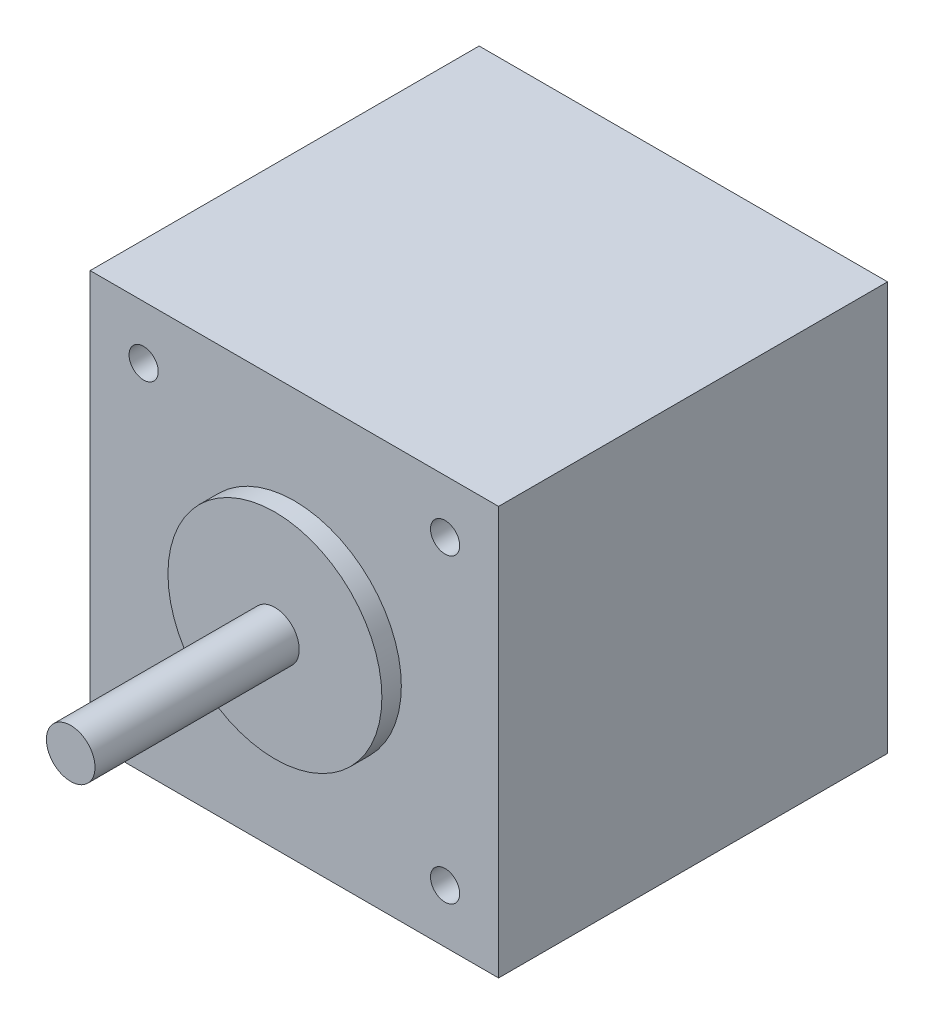
SolidWorks part; units mm, degrees
ref_plane "Спереди" through (0, 0, 0) normal (0, 0, 1) x (1, 0, 0)
ref_plane "Сверху" through (0, 0, 0) normal (0, 1, 0) x (1, 0, 0)
ref_plane "Справа" through (0, 0, 0) normal (1, 0, 0) x (0, 0, -1)
other "Configuration Table"
sketch "Эскиз1" plane through (0, 0, 0) normal (0, 0, 1) x (1, 0, 0)
  line L1 (-21, -21) -> (21, -21)
  line L2 (-21, -21) -> (-21, 21)
  line L3 (-21, 21) -> (21, 21)
  line L4 (21, -21) -> (21, 21)
  line L5 (-21, -21) -> (21, 21) construction
  line L6 (-21, 21) -> (21, -21) construction
  point P0 (0, 0)
  dimension "D1" = 42
  dimension "D2" = 42
extrude "Корпус" add sketch "Эскиз1" along normal blind 40
sketch "Эскиз2" plane through (0, 0, 0) normal (0, 0, 1) x (1, 0, 0)
  circle A0 centre (0, 0) radius 2.5
extrude "Вал_ПРЕДВ" add sketch "Эскиз2" along normal blind 63
sketch "Эскиз3" plane through (0, 0, 0) normal (0, 0, 1) x (1, 0, 0)
  circle A0 centre (0, 0) radius 11
  dimension "D1" = 22
extrude "Буртик_ПРЕДВ" add sketch "Эскиз3" along normal blind 42
sketch "Эскиз4" plane through (0, 0, 0) normal (0, 0, 1) x (1, 0, 0)
  circle A0 centre (-15.5, -15.5) radius 1.5
  circle A1 centre (-15.5, 15.5) radius 1.5
  circle A2 centre (15.5, -15.5) radius 1.5
  circle A3 centre (15.5, 15.5) radius 1.5
  dimension "D1" = 3
  dimension "D2" = 3
  dimension "D3" = 3
  dimension "D4" = 3
extrude "Крепеж_М3_ПРЕДВ" cut sketch "Эскиз4" against normal blind 4.5 from offset 40
equation "\"Мотор X ширина корпуса\"= 42.3"
equation "\"Мотор X высота корпуса\"= 42.3"
equation "\"Мотор X длина корпуса\"= 40"
equation "\"Мотор X вылет вала\"= 19.8"
equation "\"Мотор Y ширина корпуса\"= 42.3"
equation "\"Мотор Y высота корпуса\"= 42.3"
equation "\"Мотор Y длина корпуса\"= 48"
equation "\"Мотор Y вылет вала\"= 30"
equation "\"Мотор Z ширина корпуса\"= 42"
equation "\"Мотор Z высота корпуса\"= 42"
equation "\"Мотор Z длина корпуса\"= 40"
equation "\"Мотор Z вылет вала\"= 23"
equation "\"Мотор диаметр вала ПРЕДВ\"= 5"
equation "\"Мотор шаг крепления ПРЕДВ\"= 31"
equation "\"Мотор диаметр отверстий ПРЕДВ\"= 3"
equation "\"Мотор глубина отверстий ПРЕДВ\"= 4.5"
equation "\"Мотор диаметр буртика ПРЕДВ\"= 22"
equation "\"Мотор высота буртика ПРЕДВ\"= 2"
equation "\"Мотор диаметр шкива ПРЕДВ\"= 16"
equation "\"Мотор длина шкива ПРЕДВ\"= 12"
equation "\"Мотор отступ шкива ПРЕДВ\"= 5"
equation "\"Мотор X шаг градусов\"= 1.8"
equation "\"Мотор X ток А\"= 1.5"
equation "\"Мотор X сопротивление Ом\"= 1.3"
equation "\"Мотор X индуктивность мГн\"= 2"
equation "\"Мотор Y шаг градусов\"= 1.8"
equation "\"Мотор Y ток А\"= 2.2"
equation "\"Мотор Y сопротивление Ом\"= 0.9"
equation "\"Мотор Y индуктивность мГн\"= 2"
equation "\"Мотор Z шаг градусов\"= 1.8"
equation "\"Мотор Z ток А\"= 1"
equation "\"Мотор Z сопротивление Ом\"= 4"
equation "\"Мотор Z индуктивность мГн\"= 8"
equation "\"Мотор Y диаметр ротора\"= 25.78"
equation "\"D1@Эскиз1\" = \"Мотор Z ширина корпуса\""
equation "\"D2@Эскиз1\" = \"Мотор Z высота корпуса\""
equation "\"D1@Корпус\" = \"Мотор Z длина корпуса\""
equation "\"D1@Эскиз2\" = \"Мотор диаметр вала ПРЕДВ\""
equation "\"D1@Вал_ПРЕДВ\" = \"Мотор Z длина корпуса\" + \"Мотор Z вылет вала\""
equation "\"D1@Эскиз3\" = \"Мотор диаметр буртика ПРЕДВ\""
equation "\"D1@Буртик_ПРЕДВ\" = \"Мотор Z длина корпуса\" + \"Мотор высота буртика ПРЕДВ\""
equation "\"D1@Эскиз4\" = \"Мотор диаметр отверстий ПРЕДВ\""
equation "\"D2@Эскиз4\" = \"Мотор диаметр отверстий ПРЕДВ\""
equation "\"D3@Эскиз4\" = \"Мотор диаметр отверстий ПРЕДВ\""
equation "\"D4@Эскиз4\" = \"Мотор диаметр отверстий ПРЕДВ\""
equation "\"D1@Крепеж_М3_ПРЕДВ\" = \"Мотор глубина отверстий ПРЕДВ\""
equation "\"D19@Крепеж_М3_ПРЕДВ\" = \"Мотор Z длина корпуса\""
equation "\"Ширина груза\"= 160"
equation "\"Глубина груза\"= 240"
equation "\"Высота груза\"= 160"
equation "\"Ширина ячейки\"= \"Ширина груза\" + 10"
equation "\"Глубина ячейки\"= \"Глубина груза\" + 10"
equation "\"Высота ячейки\"= \"Высота груза\" + 10 + 13"
equation "\"Колво ячеек ширина\"= 2"
equation "\"Колво ячеек высота\"= 2"
equation "\"Толщина стенки\" = \"Толщина тонких панелей\""
equation "\"Крепление дверцы\"= 5 "
equation "\"Ширина рейки\"= \"Толщина шестерни\""
equation "\"Высота рейки\"= 20"
equation "\"Высота пола\" = 2*\"Толщина тонких панелей\""
equation "\"Колво полозьев\"= 5"
equation "\"Отступ рейки\"= 20"
equation "\"Глубина каретки\"= \"Глубина ячейки\" + 30 + \"Мотор Y высота корпуса\" + 20 + \"Удлинение платформы по глубине\""
equation "\"Отступ шпильки\"= 26"
equation "\"Диаметр шпильки\"= 5"
equation "\"Длинна шпильки\" = (\"Высота ячейки\"+\"Толщина горизонтальных плит\"+\"Высота пола\")*\"Колво ячеек высота\"+2*(\"Толщина горизонтальных плит\"+\"Отступ рейки\")"
equation "\"Ширина пластины\" = 50"
equation "\"Высота зона выгрузки\"= \"Высота ячейки\" * 2 + \"Толщина стенки\" * 2"
equation "\"Колво выгрузки\"= 1"
equation "\"Отступ крепления мотора фиксации\" = (70-\"Толщина вертикальных стенок\")/2"
equation "\"Диаметр оси\"= 10"
equation "\"Диаметр ролика\"= 20"
equation "\"Колво роликов\"= 10"
equation "\"Шаг роликов\"= \"Диаметр ролика\" + 20"
equation "\"Ширина ячейки выгрузки\" = \"Ширина ячейки\"+\"Толщина вертикальных стенок\"+2*\"Отступ крепления мотора фиксации\""
equation "\"Длинна рейки\" = (\"Ширина ячейки\"+\"Толщина вертикальных стенок\"+\"Крепление дверцы\")*\"Колво ячеек ширина\"+\"Ширина ячейки выгрузки\"*\"Колво выгрузки\"+\"Толщина вертикальных стенок\"+2*\"Отступ крепления мотора фиксации\"-\"Крепление дверцы\"*\"Колво ячеек ширина\""
equation "\"Толщина тонких панелей\" = 6"
equation "\"Толщина вертикальных стенок\" = 6"
equation "\"Толщина горизонтальных плит\" = 6"
equation "\"Базовая высота корпуса\"= (\"Высота ячейки\"+\"Толщина тонких панелей\"+\"Высота пола\")*\"Колво ячеек высота\"+6*\"Толщина тонких панелей\"+\"Мотор X ширина корпуса\"+\"Мотор Y ширина корпуса\"+75"
equation "\"Высота корпуса\"= (\"Высота ячейки\"+\"Толщина горизонтальных плит\"+\"Высота пола\")*\"Колво ячеек высота\"+2*\"Толщина горизонтальных плит\"+4*\"Толщина тонких панелей\"+\"Мотор X ширина корпуса\"+\"Мотор Y ширина корпуса\"+75"
equation "\"Смещение центра корпуса\"= (\"Высота корпуса\"-\"Базовая высота корпуса\")/2-(\"Толщина горизонтальных плит\"-\"Толщина тонких панелей\")"
equation "\"Отметка пола\"= -\"Базовая высота корпуса\"/2+\"Толщина тонких панелей\""
equation "\"Отметка потолка\"= \"Отметка пола\"+\"Высота корпуса\"-2*\"Толщина горизонтальных плит\""
equation "\"Отметка верхней полки\"= \"Отметка потолка\"-(28+\"Толщина тонких панелей\")-\"Высота ячейки\"-\"Высота пола\""
equation "\"Отметка нижней полки\"= \"Отметка верхней полки\"-\"Высота ячейки\"-\"Высота пола\"-\"Толщина горизонтальных плит\""
equation "\"Толщина шестерни\"= 10"
